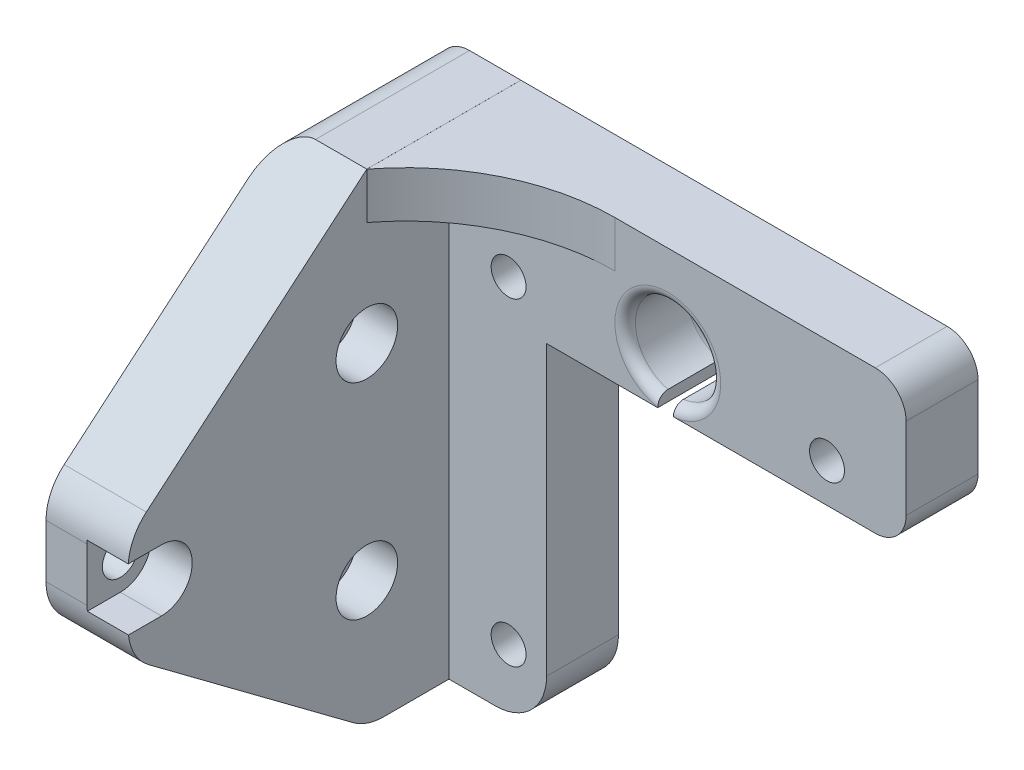
SolidWorks part; units mm, degrees
material "ABS"
ref_plane "Front Plane" through (0, 0, 0) normal (0, 0, 1) x (1, 0, 0)
ref_plane "Top Plane" through (0, 0, 0) normal (0, 1, 0) x (1, 0, 0)
ref_plane "Right Plane" through (0, 0, 0) normal (1, 0, 0) x (0, 0, -1)
ref_plane "Plane5" through (60, 0, 0) normal (1, 0, 0) x (0, 0, -1)
sketch "Sketch50" plane through (60, 0, 0) normal (1, 0, 0) x (0, 0, -1)
  line L0 (-38.2349, -28) -> (-38.2349, -38)
  line L1 (0, -55.3249) -> (-15, -55.3249)
  line L2 (0, -8.3249) -> (-15, -8.3249)
  line L4 (0, -55.3249) -> (0, -8.3249)
  line L5 (-15, -2.0171) -> (-15, -57.8143) construction
  line L9 (-38.2349, -28) -> (-15, -8.3249)
  line L10 (-38.2349, -38) -> (-15, -55.3249)
  circle A0 centre (-35, -33) radius 1.75
  circle A1 centre (-15, -23) radius 1.75
  circle A2 centre (-15, -43) radius 1.75
  dimension "D1" = 3.5
  dimension "D2" = 3.5
  dimension "D3" = 3.5
  dimension "D4" = 20
  dimension "D5" = 20
  dimension "D6" = 47
  dimension "D7" = 15
  dimension "D8" = 10
extrude "Extrude1" add sketch "Sketch50" along normal blind 8 separate body
sketch "Sketch52" plane through (0, 0, 0) normal (0, 0, -1) x (-1, 0, 0)
  line L0 (-61.5211, -55.3284) -> (-61.5211, -8.3284)
  line L1 (-112.5, -8.3284) -> (-112.5, -22.2806)
  line L2 (-61.5211, -8.3284) -> (-112.5, -8.3284)
  line L3 (-77.5, -22.2806) -> (-112.5, -22.2806)
  line L4 (-61.5211, -55.3284) -> (-77.5, -55.3284)
  line L5 (-77.5, -55.3249) -> (-77.5, -8.3249)
  line L6 (-77.5, -55.3284) -> (-77.5, -22.2806)
  circle A0 centre (-89.3, -17.2) radius 4.15
  circle A1 centre (-73.8015, -18.5) radius 1.7
  circle A2 centre (-104.8, -18.5) radius 1.7
  circle A3 centre (-73.8015, -49.5086) radius 1.7
  point P3 (-113, -87.5802)
  point P9 (-74.0211, -54.9585)
  point P10 (-74.0211, -7.7617)
  dimension "D2" = 47
  dimension "D4" = 3.4
  dimension "D3" = 8.3
  dimension "D5" = 15.9789
  dimension "D1" = 9.5
extrude "Extrude2" add sketch "Sketch52" against normal blind 7
fillet "Fillet1" radius 3 2 edges at (112.5, -22.2806, 3.5) (112.5, -8.3284, 3.5)
fillet "Fillet2" radius 5 1 edges at (77.5, -55.3284, 3.5)
sketch "Sketch54" plane through (0, -8.3284, 0) normal (0, 1, 0) x (1, 0, 0)
  line L0 (68, -7) -> (109.5, -7) construction
  line L1 (68, -15) -> (68, -7)
  line L2 (68, -15) -> (68, -38.2349) construction
  line L3 (68, 0) -> (68, -15) construction
  line L4 (68, -7) -> (84.1795, -7)
  arc A0 (84.1795, -7) -> (68, -15) centre (84.1795, -27.3609) ccw
extrude "Extrude3" add sketch "Sketch54" against normal blind 4.5
fillet "Fillet4" radius 5 3 edges at (64, -28, 38.2349) (64, -38, 38.2349) (64, -55.3249, 15)
fillet "Fillet5" radius 3 1 edges at (60, -8.3249, 7.5)
sketch "Sketch55" plane through (68, 0, 0) normal (1, 0, 0) x (0, 0, -1)
  line L0 (-35, -30) -> (-38.7879, -30)
  line L1 (-38.7879, -30) -> (-38.7879, -36)
  line L2 (-35, -36) -> (-38.7879, -36)
  arc A0 (-35, -36) -> (-35, -30) centre (-35, -33) ccw
  circle A1 centre (-15, -23) radius 3
  circle A2 centre (-15, -43) radius 3
  dimension "D1" = 6
  dimension "D2" = 6
  dimension "D3" = 6
extrude "Cut-Extrude3" cut sketch "Sketch55" against normal blind 4
sketch "Sketch56" plane through (0, 0, 0) normal (0, 0, -1) x (-1, 0, 0)
  line L0 (-109.5, -22.2806) -> (-77.5, -22.2806) construction
  line L1 (-89.3173, -23.6005) -> (-88.3204, -23.6005)
  line L2 (-89.3173, -23.6005) -> (-89.3173, -20.9607)
  line L3 (-89.3173, -20.9607) -> (-88.3204, -20.9607)
  line L4 (-88.3204, -23.6005) -> (-88.3204, -20.9607)
  line L5 (-89.3173, -23.6005) -> (-88.3204, -20.9607) construction
  line L6 (-89.3173, -20.9607) -> (-88.3204, -23.6005) construction
  point P0 (-88.8189, -22.2806)
fillet "Fillet9" radius 1 1 edges at (89.3, -13.05, 0)
fillet "Fillet10" radius 1 1 edges at (89.3, -13.05, 7)
sketch "Sketch57" plane through (0, -22.2806, 0) normal (0, -1, 0) x (1, 0, 0)
  line L0 (88.8276, 7.5275) -> (89.8276, 7.5275)
  line L2 (89.8276, -0.6284) -> (89.8276, 7.5275)
  line L3 (88.8276, -0.6284) -> (88.8276, 7.5275)
  line L4 (88.8276, -0.6284) -> (89.8276, -0.6284)
extrude "Extrude4" cut sketch "Sketch57" against normal blind 4
extrude "Cut-Extrude4" cut sketch "Sketch56" against normal up to surface (7 mm away) up to face at (85.3186, -28.299, 7)
